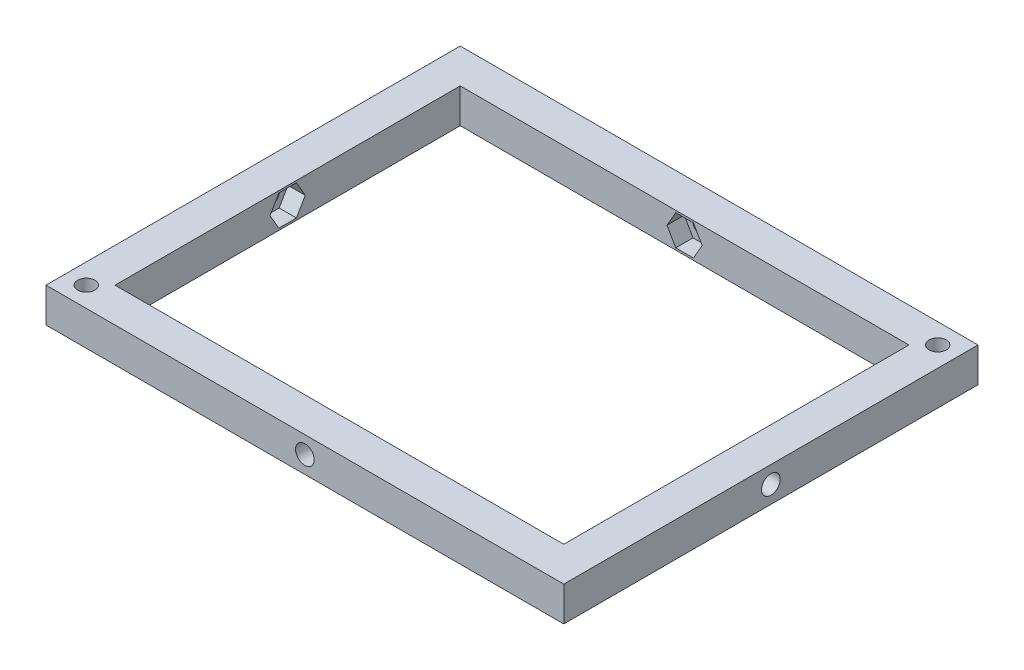
SolidWorks part; units mm, degrees
other "Marca1"
sketch "Croquis7" plane through (-45, 6, 36) normal (-0.6148, 0.4466, 0.6501) x (0.7881, 0.3153, 0.5287)
ref_plane "Alzado" through (0, 0, 0) normal (0, 0, 1) x (1, 0, 0)
ref_plane "Planta" through (0, 0, 0) normal (0, 1, 0) x (1, 0, 0)
ref_plane "Vista lateral" through (0, 0, 0) normal (1, 0, 0) x (0, 0, -1)
sketch "Croquis1" plane through (0, 0, 0) normal (0, 1, 0) x (1, 0, 0)
  line L1 (-45, -36) -> (45, -36)
  line L2 (-45, -36) -> (-45, 36)
  line L3 (-45, 36) -> (45, 36)
  line L4 (45, -36) -> (45, 36)
  line L5 (-45, -36) -> (45, 36) construction
  line L6 (-45, 36) -> (45, -36) construction
  point P0 (0, 0)
  dimension "D1" = 90
  dimension "D2" = 72
extrude "Saliente-Extruir1" add sketch "Croquis1" along normal blind 6
sketch "Croquis2" plane through (0, 6, 0) normal (0, 1, 0) x (1, 0, 0)
  line L0 (-45, 36) -> (-45, -36) construction
  line L1 (-39, -30) -> (39, -30)
  line L2 (-39, -30) -> (-39, 30)
  line L3 (-39, 30) -> (39, 30)
  line L4 (39, -30) -> (39, 30)
  line L5 (-39, -30) -> (39, 30) construction
  line L6 (-39, 30) -> (39, -30) construction
  line L7 (-45, -36) -> (45, -36) construction
  line L8 (45, 36) -> (-45, 36) construction
  line L10 (45, -36) -> (45, 36) construction
  circle A0 centre (-41.5, -32.5) radius 1.5
  circle A1 centre (41.5, 32.5) radius 1.5
  point P0 (0, 0)
  dimension "D3" = 3
  dimension "D4" = 3.5
  dimension "D5" = 3.5
  dimension "D6" = 3.5
  dimension "D7" = 3.5
  dimension "D8" = 3
  dimension "D1" = 78
  dimension "D2" = 60
extrude "Cortar-Extruir1" cut sketch "Croquis2" against normal through all
sketch "Croquis3" plane through (0, 6, 0) normal (0, 1, 0) x (1, 0, 0)
  line L0 (-45, -36) -> (45, -36) construction
  line L1 (-39.97, -29.85) -> (-43.03, -29.85)
  line L2 (-43.03, -29.85) -> (-44.56, -32.5)
  line L3 (-44.56, -32.5) -> (-43.03, -35.15)
  line L4 (-43.03, -35.15) -> (-39.97, -35.15)
  line L5 (-39.97, -35.15) -> (-38.44, -32.5)
  line L6 (-38.44, -32.5) -> (-39.97, -29.85)
  line L7 (-45, 36) -> (-45, -36) construction
  line L8 (45, -36) -> (45, 36) construction
  line L9 (43.03, 35.15) -> (39.97, 35.15)
  line L10 (39.97, 35.15) -> (38.44, 32.5)
  line L11 (38.44, 32.5) -> (39.97, 29.85)
  line L12 (39.97, 29.85) -> (43.03, 29.85)
  line L13 (43.03, 29.85) -> (44.56, 32.5)
  line L14 (44.56, 32.5) -> (43.03, 35.15)
  line L15 (45, 36) -> (-45, 36) construction
  circle A0 centre (-41.5, -32.5) radius 2.65 construction
  circle A1 centre (41.5, 32.5) radius 2.65 construction
  dimension "D1" = 5.3
  dimension "D2" = 3.5
  dimension "D3" = 3.5
  dimension "D4" = 5.3
  dimension "D5" = 3.5
  dimension "D6" = 3.5
extrude "Cortar-Extruir2" cut sketch "Croquis3" along normal blind 3 from surface starting at face at (41.5, 0, -31)
sketch "Croquis4" plane through (0, 0, 36) normal (0, 0, 1) x (1, 0, 0)
  line L0 (-45, 3) -> (45, 3) construction
  line L1 (-45, 6) -> (-45, 0) construction
  line L2 (45, 6) -> (45, 0) construction
  line L3 (-45, 0) -> (45, 0) construction
  line L4 (0, 6) -> (0, 0) construction
  line L5 (-45, 6) -> (45, 6) construction
  circle A0 centre (0, 3) radius 1.625
  point P15 (0, 3)
  dimension "D1" = 3.25
extrude "Cortar-Extruir3" cut sketch "Croquis4" against normal through all
sketch "Croquis5" plane through (45, 0, 0) normal (1, 0, 0) x (0, 0, -1)
  line L0 (-36, 3) -> (36, 3) construction
  line L1 (-36, 6) -> (-36, 0) construction
  line L2 (36, 6) -> (36, 0) construction
  line L3 (0, 6) -> (0, 0) construction
  line L4 (-36, 6) -> (36, 6) construction
  circle A0 centre (0, 3) radius 1.625
  dimension "D1" = 3.25
extrude "Cortar-Extruir4" cut sketch "Croquis5" against normal through all
sketch "Croquis6" plane through (0, 0, 36) normal (0, 0, 1) x (1, 0, 0)
  line L0 (-45, 3) -> (45, 3) construction
  line L1 (1.53, 5.65) -> (-1.53, 5.65)
  line L2 (-1.53, 5.65) -> (-3.06, 3)
  line L3 (-3.06, 3) -> (-1.53, 0.35)
  line L4 (-45, 0) -> (45, 0)
  line L5 (45, 0) -> (45, 6)
  line L6 (45, 6) -> (-45, 6)
  line L7 (-45, 6) -> (-45, 0)
  line L8 (-45, 0) -> (45, 0)
  line L9 (45, 0) -> (45, 6)
  line L10 (45, 6) -> (-45, 6)
  line L11 (-45, 6) -> (-45, 0)
  line L12 (-1.53, 0.35) -> (1.53, 0.35)
  line L13 (1.53, 0.35) -> (3.06, 3)
  line L14 (3.06, 3) -> (1.53, 5.65)
  circle A0 centre (0, 3) radius 2.65 construction
  point P2 (0, 3)
  dimension "D2" = 5.3
  dimension "D1" = 0
extrude "Cortar-Extruir5" cut sketch "Croquis6" along normal blind 3 from surface flip side to cut starting at face at (1.625, 3, 30)
sketch "Croquis8" plane through (-45, 0, 0) normal (-1, 0, 0) x (0, 0, 1)
  line L0 (0, 6) -> (0, 0) construction
  line L1 (1.53, 5.65) -> (-1.53, 5.65)
  line L2 (-1.53, 5.65) -> (-3.06, 3)
  line L3 (-3.06, 3) -> (-1.53, 0.35)
  line L4 (-1.53, 0.35) -> (1.53, 0.35)
  line L5 (1.53, 0.35) -> (3.06, 3)
  line L6 (3.06, 3) -> (1.53, 5.65)
  circle A0 centre (0, 3) radius 2.65 construction
  point P0 (0, 3)
  dimension "D1" = 5.3
extrude "Cortar-Extruir6" cut sketch "Croquis8" along normal blind 3 from surface starting at face at (-39, 3, 1.625)
extrude "Cortar-Extruir7" cut sketch "Croquis8<3>" against normal blind 3 from surface starting at face at (39, 3, -1.625)
sketch "Croquis8<3>" plane through (-45, 0, 0) normal (-1, 0, 0) x (0, 0, 1) same geometry as "Croquis8"
extrude "Cortar-Extruir8" cut sketch "Croquis6<2>" against normal blind 3 from surface flip side to cut starting at face at (-1.625, 3, -30)
sketch "Croquis6<2>" plane through (0, 0, 36) normal (0, 0, 1) x (1, 0, 0) same geometry as "Croquis6"
